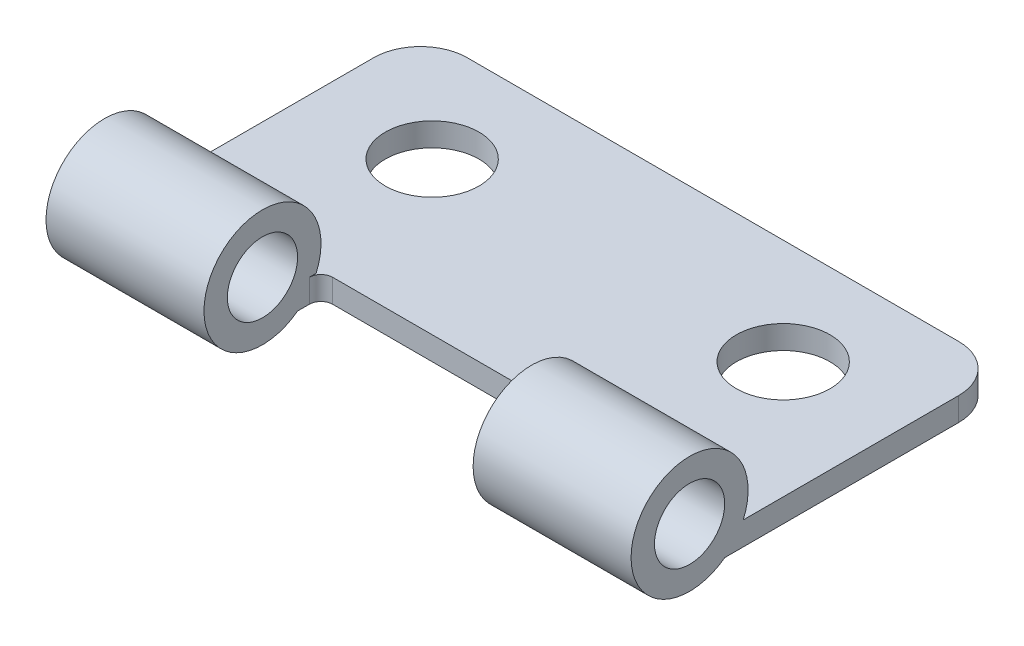
SolidWorks part; units mm, degrees
ref_plane "前视基准面" through (0, 0, 0) normal (0, 0, 1) x (1, 0, 0)
ref_plane "上视基准面" through (0, 0, 0) normal (0, 1, 0) x (1, 0, 0)
ref_plane "右视基准面" through (0, 0, 0) normal (1, 0, 0) x (0, 0, -1)
other "Configuration Table"
sketch "草图1" plane through (0, 0, 0) normal (0, 1, 0) x (1, 0, 0)
  line L0 (-5.75, 0) -> (5.75, 0) construction
  line L1 (-5.75, 0) -> (-5.75, 1)
  line L2 (-5.75, 1) -> (-12.5, 1) construction
  line L3 (-12.5, 1) -> (-12.5, 12)
  line L4 (-12.5, 12) -> (12.5, 12)
  line L5 (12.5, 12) -> (12.5, 1)
  line L6 (12.5, 1) -> (5.75, 1) construction
  line L7 (5.75, 1) -> (5.75, 0)
  line L8 (0, 0) -> (0, 12) construction
  line L9 (-12.5, 1) -> (-12.5, 0)
  line L10 (-12.5, 0) -> (-5.75, 0)
  line L11 (5.75, 0) -> (12.5, 0)
  line L12 (12.5, 0) -> (12.5, 1)
  line L13 (-5.75, 1) -> (5.75, 1)
  line L14 (-12.5, 7.5) -> (12.5, 7.5) construction
  circle A0 centre (-7.5, 7.5) radius 2
  circle A1 centre (7.5, 7.5) radius 2
  point P2 (0, 0)
  dimension "D5" = 4
  dimension "D1" = 25
  dimension "D2" = 11
  dimension "D3" = 1
  dimension "D4" = 11.5
  dimension "D6" = 15
  dimension "D7" = 4.5
extrude "凸台-拉伸1" add sketch "草图1" along normal blind 1
fillet "圆角1" radius 2 2 edges at (-12.5, 0.5, -12) (12.5, 0.5, -12)
fillet "圆角2" radius 0.5 2 edges at (5.75, 0.5, -1) (-5.75, 0.5, -1)
sketch "草图2" plane through (0, 0, 0) normal (1, 0, 0) x (0, 0, -1)
  line L0 (1, 1) -> (1, 0) construction
  circle A0 centre (-1.5, 2) radius 1.5
  circle A1 centre (-1.5, 2) radius 2.5
  dimension "D1" = 5
  dimension "D2" = 3
  dimension "D3" = 2.5
extrude "凸台-拉伸2" add sketch "草图2" against normal up to surface (12.5 mm away) from surface up to face at (-12.5, 0.5, -5) starting at face at (-5.75, 0.5, -0.25)
extrude "凸台-拉伸3" add sketch "草图2<3>" along normal up to surface (12.5 mm away) from surface up to face at (12.5, 0.5, -5) starting at face at (5.75, 0.5, -0.25)
sketch "草图2<3>" plane through (0, 0, 0) normal (1, 0, 0) x (0, 0, -1) same geometry as "草图2"
